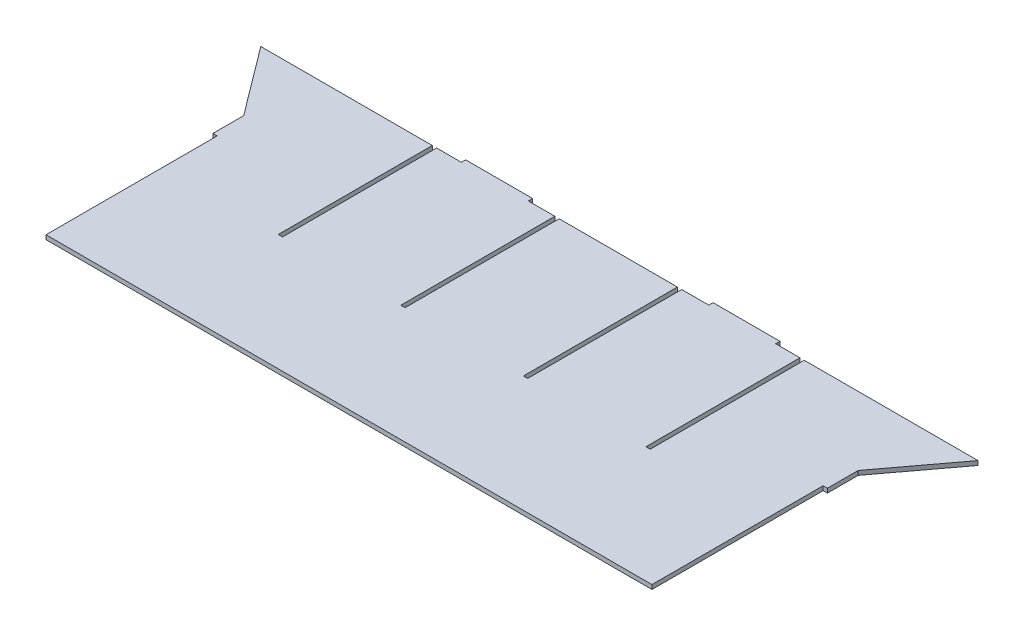
SolidWorks part; units mm, degrees
material "Custom Plastic"
ref_plane "X-Y Datum" through (0, 0, 0) normal (0, 0, 1) x (1, 0, 0)
ref_plane "X-Z Datum" through (0, 0, 0) normal (0, 1, 0) x (1, 0, 0)
ref_plane "Y-Z Datum" through (0, 0, 0) normal (1, 0, 0) x (0, 0, -1)
sketch "Sketch1" plane through (0, 0, 0) normal (0, 0, 1) x (1, 0, 0)
  line L1 (-227.966, -1.5875) -> (227.966, -1.5875)
  line L2 (-227.966, -1.5875) -> (-227.966, 1.5875)
  line L3 (-227.966, 1.5875) -> (227.966, 1.5875)
  line L4 (227.966, -1.5875) -> (227.966, 1.5875)
  line L5 (-227.966, -1.5875) -> (227.966, 1.5875) construction
  line L6 (-227.966, 1.5875) -> (227.966, -1.5875) construction
  point P0 (0, 0)
  dimension "D1" = 3.175
  dimension "D2" = 455.932
extrude "Boss-Extrude1" add sketch "Sketch1" along normal blind 200.642
sketch "Sketch2" plane through (0, 1.5875, 0) normal (0, 1, 0) x (1, 0, 0)
  line L0 (227.966, 0) -> (224.791, 0)
  line L1 (227.966, 0) -> (-227.966, 0) construction
  line L2 (224.791, 0) -> (137.161, 0)
  line L3 (137.161, 0) -> (133.986, 0)
  line L10 (133.986, 0) -> (137.161, 0)
  line L11 (133.986, 0) -> (133.986, -114.3)
  line L12 (133.986, -114.3) -> (137.161, -114.3)
  line L13 (137.161, 0) -> (137.161, -114.3)
  line M2 (227.966, 0) -> (-227.966, 0)
  dimension "D1" = 87.63
  dimension "D2" = 3.175
  dimension "D3" = 114.3
extrude "Cut-Extrude1" cut sketch "Sketch2" against normal through all contours L13 L11 L12 M2 region at (135.5735, 1.5875, 57.15)
pattern_linear "LPattern1" count 4 spacing 90.932 along (-1, 0, 0) of "Cut-Extrude1"
sketch "Sketch3" plane through (0, 0, 0) normal (0, 0, -1) x (-1, 0, 0)
  line L1 (-115.966, 1.5875) -> (-66.3072, 1.5875)
  line L2 (-115.966, 1.5875) -> (-115.966, -1.5875)
  line L3 (-115.966, -1.5875) -> (-66.3072, -1.5875)
  line L4 (-66.3072, 1.5875) -> (-66.3072, -1.5875)
  line L5 (67.5982, 1.5875) -> (117.257, 1.5875)
  line L6 (67.5982, 1.5875) -> (67.5982, -1.5875)
  line L7 (67.5982, -1.5875) -> (117.257, -1.5875)
  line L8 (117.257, 1.5875) -> (117.257, -1.5875)
extrude "Boss-Extrude2" add sketch "Sketch3" along normal blind 3.175
sketch "Sketch4" plane through (0, -1.5875, 0) normal (0, -1, 0) x (1, 0, 0)
  line L0 (-227.966, 0) -> (-266.066, 0)
  line L1 (-266.066, 0) -> (-227.966, 50.8)
  line L2 (-227.966, 200.642) -> (-227.966, 0) construction
  line L3 (-227.966, 50.8) -> (-227.966, 0)
  dimension "D1" = 38.1
  dimension "D2" = 50.8
extrude "Boss-Extrude3" add sketch "Sketch4" against normal blind 3.175
mirror "Mirror1" about plane through (0, 0, 0) normal (1, 0, 0) of "Boss-Extrude3"
sketch "Sketch5" plane through (0, -1.5875, 0) normal (0, -1, 0) x (1, 0, 0)
  line L1 (-227.966, 200.642) -> (-224.791, 200.642)
  line L2 (-227.966, 200.642) -> (-227.966, 73.642)
  line L3 (-227.966, 73.642) -> (-224.791, 73.642)
  line L4 (-224.791, 200.642) -> (-224.791, 73.642)
  dimension "D1" = 3.175
  dimension "D2" = 127
extrude "Cut-Extrude2" cut sketch "Sketch5" against normal blind 3.175
mirror "Mirror2" about plane through (0, 0, 0) normal (1, 0, 0) of "Cut-Extrude2"
